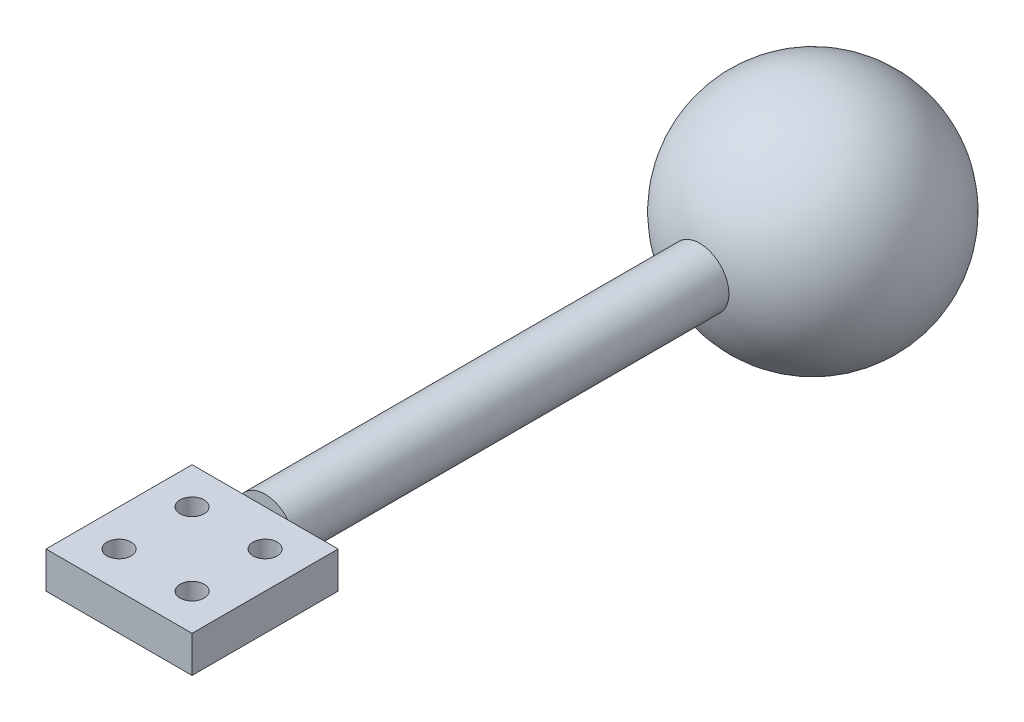
SolidWorks part; units mm, degrees
ref_plane "Front Plane" through (0, 0, 0) normal (0, 0, 1) x (1, 0, 0)
ref_plane "Top Plane" through (0, 0, 0) normal (0, 1, 0) x (1, 0, 0)
ref_plane "Right Plane" through (0, 0, 0) normal (1, 0, 0) x (0, 0, -1)
sketch "Sketch1" plane through (0, 0, 0) normal (0, 0, 1) x (1, 0, 0)
  line L0 (0, 16) -> (0, -16) construction
  circle A0 centre (0, 0) radius 16
  circle A1 centre (0, 0) radius 4
  dimension "D1" = 32
  dimension "D2" = 8
revolve "Revolve7" add sketch "Sketch1" angle 360 about L0 region at (-15.5475, 0, 0)
extrude "Boss-Extrude1" add sketch "Sketch1<3>" along normal blind 75 contours A1
sketch "Sketch1<3>" plane through (0, 0, 0) normal (0, 0, 1) x (1, 0, 0) same geometry as "Sketch1"
sketch "Sketch2" plane through (0, 0, 0) normal (0, 1, 0) x (1, 0, 0)
  line L0 (0, -75) -> (-10, -75)
  line L1 (-4, -75) -> (4, -75) construction
  line L2 (-10, -75) -> (-10, -85)
  line L3 (-10, -85) -> (10, -85)
  line L4 (10, -95) -> (10, -75)
  line L5 (10, -75) -> (0, -75)
  line L6 (0, -75) -> (0, -85) construction
  line L7 (-10, -80) -> (0, -80) construction
  line L8 (-5, -75) -> (-5, -85) construction
  line L9 (10, -95) -> (0, -95)
  line L10 (0, -95) -> (-10, -95)
  line L11 (-10, -95) -> (-10, -85)
  circle A4 centre (-5, -80) radius 1.65
  circle A5 centre (5, -80) radius 1.65
  circle A6 centre (5, -90) radius 1.65
  circle A7 centre (-5, -90) radius 1.65
  point P23 (0, 0)
  dimension "D4" = 3.3
  dimension "D5" = 5
  dimension "D1" = 20
  dimension "D2" = 10
  dimension "D3" = 10
extrude "Boss-Extrude2" add sketch "Sketch2" along normal blind 2.5 and the other way blind 2.5 contours L11 L10 L9 L4 L3 A6 A7 | L4 L5 L0 L2 L3 A4 A5 region at (0, 0, 80) region at (0, 0, 90)
